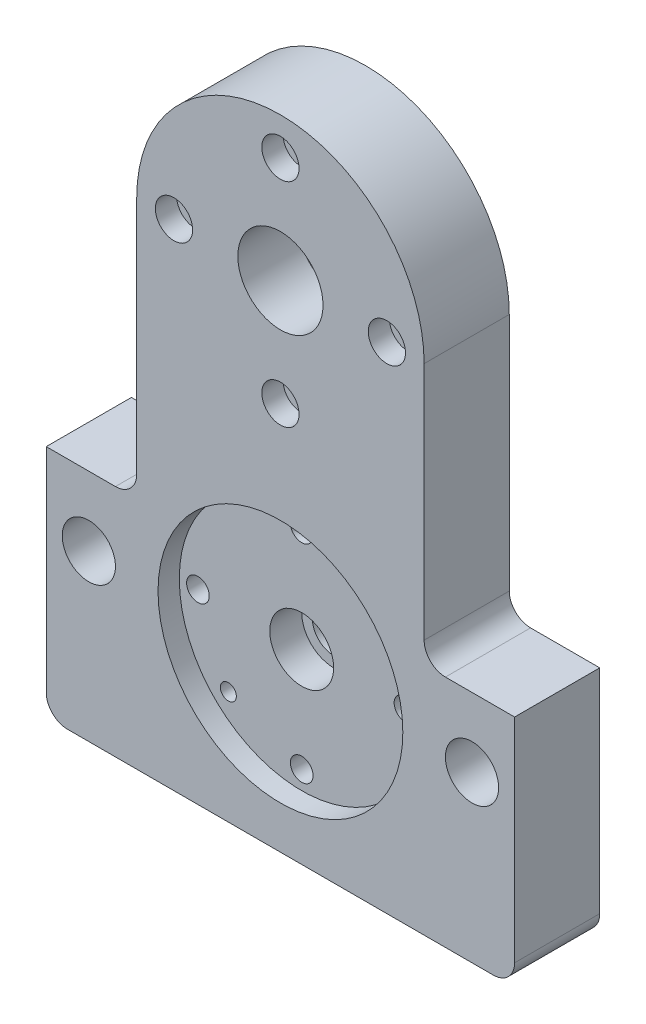
SolidWorks part; units mm, degrees
note: '?' marks a value the reader was unsure of.
material "6061 Alloy"
ref_plane "Front" through (0, 0, 0) normal (0, 0, 1) x (1, 0, 0)
ref_plane "Top" through (0, 0, 0) normal (0, 1, 0) x (1, 0, 0)
ref_plane "Right" through (0, 0, 0) normal (1, 0, 0) x (0, 0, -1)
ref_axis "Axis" through (0, 0, -80.9) along (0, 0, 1)?
sketch "Bolt circle" plane through (0, 0, 0) normal (0, 0, 1) x (1, 0, 0)
  line L0 (0, 36.5125) -> (0, 25.4) construction
  line L1 (-42.8625, 0) -> (-42.8625, -77.7875)
  line L3 (42.8625, 0) -> (42.8625, -77.7875)
  line L7 (42.8625, -77.7875) -> (69.85, -77.7875)
  line L12 (-42.8625, -77.7875) -> (-69.85, -77.7875)
  line L30 (69.85, -77.7875) -> (69.85, -147.6375)
  line L31 (69.85, -147.6375) -> (-69.85, -147.6375)
  line L34 (-69.85, -77.7875) -> (-69.85, -147.6375)
  line L35 (0, 0) -> (0, -147.6375) construction
  circle A0 centre (0, 0) radius 36.5125 construction
  circle A1 centre (0, 0) radius 25.4 construction
  circle A2 centre (0, 0) radius 30.9562 construction
  arc A5 (-42.8625, 0) -> (42.8625, 0) centre (0, 0) cw
  circle A7 centre (0, 0) radius 12.7
  circle A8 centre (0, -98.425) radius 36.5125 construction
  circle A9 centre (0, -98.425) radius 6.35
  point P0 (0, -36.5125)
  point P7 (0, 30.9562)
  point P9 (0, -134.9375)
  point P34 (0, 42.8625)
  dimension "D1" = 73.025
  dimension "D2" = 50.8
  dimension "D3" = 69.85
  dimension "D12" = 139.7
  dimension "D13" = 25.4
  dimension "D18" = 12.7
  dimension "D4" = 98.425
  dimension "D7" = 85.725
  dimension "D16" = 6.35
  dimension "D17" = 12.7
extrude "Base" add sketch "Bolt circle" along normal mid plane 25.4
hole_wizard "Structure tube connection counterbore" positions "Sketch15" profile "Sketch14" counterbore size "1/4" standard "Ansi Inch" end condition through all
sketch "Sketch15" plane through (0, 0, -12.7) normal (0, 0, -1) x (-1, 0, 0)
  circle A0 centre (0, -98.425) radius 30.9563 construction
  point P1 (0, -67.4688)
  dimension "D1" = 61.9125
sketch "Sketch14" plane through (0, -67.4688, -12.7) normal (1, 0, 0) x (0, 1, 0)
  line L0 (0, 0) -> (0, 25.4)
  line L1 (0, 25.4) -> (3.3782, 25.4)
  line L3 (3.3782, 25.4) -> (3.3782, 6.35)
  line L4 (3.3782, 6.35) -> (5.5562, 6.35)
  line L5 (5.5562, 6.35) -> (5.5562, 0)
  line L7 (5.5562, 0) -> (0, 0)
  line L11 (0, -6.35) -> (0, 107.95) construction
  dimension "Thru Hole Dia." = 6.7564
  dimension "Thru Hole Depth" = 25.4
  dimension "C'Bore Dia." = 11.1125
  dimension "C'Bore Depth" = 6.35
cosmetic thread "Hole Thread1" parameters "D1"=0, "D2"=4010
pattern_circular "Structure tube connection counterbore pattern" count 4 over 360 about axis through (0, -98.425, 0) along (0, 0, 1) of "Structure tube connection counterbore"
hole_wizard "Spindle connection counterbore" positions "Sketch11" profile "Sketch10" counterbore size "1/4" standard "Ansi Inch" end condition through all
sketch "Sketch11" plane through (0, 0, 12.7) normal (0, 0, 1) x (1, 0, 0)
  circle A0 centre (0, 0) radius 31.75 construction
  point P0 (0, 31.75)
  dimension "D1" = 63.5
sketch "Sketch10" plane through (0, 31.75, 12.7) normal (1, 0, 0) x (0, -1, 0)
  line L0 (0, 0) -> (0, 25.4)
  line L1 (0, 25.4) -> (3.3782, 25.4)
  line L3 (3.3782, 25.4) -> (3.3782, 6.35)
  line L4 (3.3782, 6.35) -> (5.5562, 6.35)
  line L5 (5.5562, 6.35) -> (5.5562, 0)
  line L7 (5.5562, 0) -> (0, 0)
  line L11 (0, -6.35) -> (0, 107.95) construction
  dimension "Thru Hole Dia." = 6.7564
  dimension "Thru Hole Depth" = 25.4
  dimension "C'Bore Dia." = 11.1125
  dimension "C'Bore Depth" = 6.35
pattern_circular "Spindle connection counterbore pattern" count 4 over 360 about axis through (0, 0, 0) along (0, 0, 1) of "Spindle connection counterbore"
sketch "Sketch16" plane through (0, 0, 12.7) normal (0, 0, 1) x (1, 0, 0)
  circle A0 centre (0, -98.425) radius 36.5125
  dimension "D1" = 73.025
extrude "Structure tube mounting pocket" cut sketch "Sketch16" against normal blind 6.35
sketch "Sketch17" plane through (0, 0, -12.7) normal (0, 0, -1) x (-1, 0, 0)
  circle A0 centre (0, 0) radius 36.5125
  circle A1 centre (0, -98.425) radius 36.5125 construction
  dimension "D1" = 73.025
extrude "Spindle mounting pocket" cut sketch "Sketch17" against normal blind 7.62
sketch "Sketch18" plane through (0, 0, 6.35) normal (0, 0, 1) x (1, 0, 0)
  circle A0 centre (0, -98.425) radius 9.525
  dimension "D1" = 19.05
extrude "Lead screw through hole" cut sketch "Sketch18" against normal blind 9.525
sketch "Sketch20" plane through (0, 0, 12.7) normal (0, 0, 1) x (1, 0, 0)
  line L1 (57.15, -98.425) -> (-57.15, -98.425) construction
  circle A0 centre (57.15, -98.425) radius 7.9375
  circle A1 centre (-57.15, -98.425) radius 7.9375
  dimension "D2" = 114.3
  dimension "D3" = 15.875
extrude "Rail mounting pilot_holes" cut sketch "Sketch20" against normal through all
sketch "Sketch27" plane through (0, 0, 6.35) normal (0, 0, 1) x (1, 0, 0)
  line L0 (20.6813, -74.3354) -> (19.6028, -75.5003)
  line L1 (24.176, -77.571) -> (23.0974, -78.7359)
  line L2 (21.8894, -76.5356) -> (-21.8894, -120.3144) construction
  line L3 (20.1421, -74.9178) -> (23.6367, -78.1534) construction
  line L4 (50, 0) -> (-50, 0) construction
  circle A0 centre (-21.8894, -120.3144) radius 2.3813
  arc A1 (24.176, -77.571) -> (20.6813, -74.3354) centre (22.4286, -75.9532) ccw
  arc A2 (23.0974, -78.7359) -> (19.6028, -75.5003) centre (21.3501, -77.1181) cw
  circle A3 centre (21.8894, -76.5356) radius 2.3813 construction
  circle A4 centre (0, -98.425) radius 30.9563 construction
  point P10 (20.1421, -74.9178)
  dimension "D2" = 45
  dimension "D3" = 4.7625
  dimension "D1" = 1.5875
extrude "Alignment_features" cut sketch "Sketch27" against normal blind 6.35
fillet "Generic_rounding_fillet" radius 6.35 4 edges at (42.8625, -77.7875, 0) (-42.8625, -77.7875, 0) (-69.85, -147.6375, 0) (69.85, -147.6375, 0)
sketch "Sketch21" plane through (0, -147.6375, 0) normal (0, -1, 0) x (1, 0, 0)
  line L0 (69.85, 0) -> (-69.85, 0) construction
  line L1 (69.85, 12.7) -> (69.85, -12.7) construction
  line L2 (-69.85, 12.7) -> (-69.85, -12.7) construction
  line L3 (0, -12.7) -> (0, 12.7) construction
  line L4 (-69.85, -12.7) -> (69.85, -12.7) construction
  line L5 (-69.85, 12.7) -> (69.85, 12.7) construction
  circle A0 centre (57.15, 0) radius 4.7625
  circle A1 centre (-57.15, 0) radius 4.7625
  dimension "D1" = 9.525
  dimension "D2" = 114.3
extrude "Point_mount_bores" [suppressed] cut sketch "Sketch21" against normal blind 6.35
sketch "Sketch22" plane through (0, 0, 12.7) normal (0, 0, 1) x (1, 0, 0)
  line L0 (69.85, -77.7875) -> (49.2125, -77.7875) construction
  line L1 (56.7531, -77.7875) -> (57.5469, -77.7875)
  line L2 (56.7531, -77.7875) -> (56.7531, -111.125)
  line L3 (57.15, -111.125) -> (57.15, -98.425) construction
  line L4 (57.5469, -77.7875) -> (57.5469, -111.125)
  line L5 (0, -147.6375) -> (0, 42.8625) construction
  line L6 (-69.85, -147.6375) -> (69.85, -147.6375) construction
  line L7 (-57.15, -111.125) -> (-57.15, -98.425) construction
  line L8 (-57.5469, -77.7875) -> (-57.5469, -111.125)
  line L9 (-56.7531, -77.7875) -> (-56.7531, -111.125)
  line L10 (-56.7531, -77.7875) -> (-57.5469, -77.7875)
  arc A0 (56.7531, -111.125) -> (57.5469, -111.125) centre (57.15, -111.125) ccw
  arc A1 (42.8625, 0) -> (-42.8625, 0) centre (0, 0) ccw construction
  arc A2 (-56.7531, -111.125) -> (-57.5469, -111.125) centre (-57.15, -111.125) cw
  dimension "D1" = 0.7937
  dimension "D2" = 12.7
extrude "Flexure_clamp_slits" [suppressed] cut sketch "Sketch22" against normal through all
hole_wizard "Flexure_clamp_counterbore" [suppressed] positions "Sketch24" profile "Sketch23" counterbore size "1/4" standard "Ansi Inch"
sketch "Sketch24" plane through (69.85, 0, 0) normal (1, 0, 0) x (0, 0, -1)
  line L0 (0, 50) -> (0, -50) construction
  line L1 (-12.7, -77.7875) -> (12.7, -77.7875) construction
  point P0 (0, -85.725)
  dimension "D1" = 7.9375
sketch "Sketch23" plane through (69.85, -85.725, 0) normal (0, 1, 0) x (0, 0, -1)
  line L0 (0, 0) -> (0, 126.6031)
  line L1 (0, 126.6031) -> (3.3782, 126.6031)
  line L3 (3.3782, 126.6031) -> (3.3782, 6.35)
  line L4 (3.3782, 6.35) -> (5.5562, 6.35)
  line L5 (5.5562, 6.35) -> (5.5562, 0)
  line L7 (5.5562, 0) -> (0, 0)
  line L11 (0, -6.35) -> (0, 107.95) construction
  dimension "Thru Hole Dia." = 6.7564
  dimension "Thru Hole Depth" = 126.6031
  dimension "C'Bore Dia." = 11.1125
  dimension "C'Bore Depth" = 6.35
hole_wizard "Flexure_clamp_threads" [suppressed] positions "Sketch26" profile "Sketch25" tap size "1/4-20" standard "Ansi Inch"
sketch "Sketch26" [suppressed] plane through (56.7531, 0, 0) normal (1, 0, 0) x (0, 0, -1)
  point P1 (0, -85.725)
sketch "Sketch25" plane through (56.7531, -85.725, 0) normal (0, 1, 0) x (0, 0, -1)
  line L0 (0, 0) -> (0, 18.0438)
  line L1 (0, 18.0438) -> (2.5527, 16.51)
  line L2 (2.5527, 16.51) -> (2.5527, 0)
  line L5 (2.5527, 0) -> (0, 0)
  line L10 (0, 18.0438) -> (-2.5527, 16.51) construction
  line L11 (0, -6.35) -> (0, 107.95) construction
  dimension "Tap Drill Dia." = 5.1054
  dimension "Tap Drill Depth" = 16.51
  dimension "Drill Angle" = 118
cosmetic thread "Hole Thread2" [suppressed] parameters "D1"=12.7, "D2"=6.35
mirror "Flexure_clamp_fastener_holes" [suppressed] about plane through (0, 0, 0) normal (1, 0, 0)
